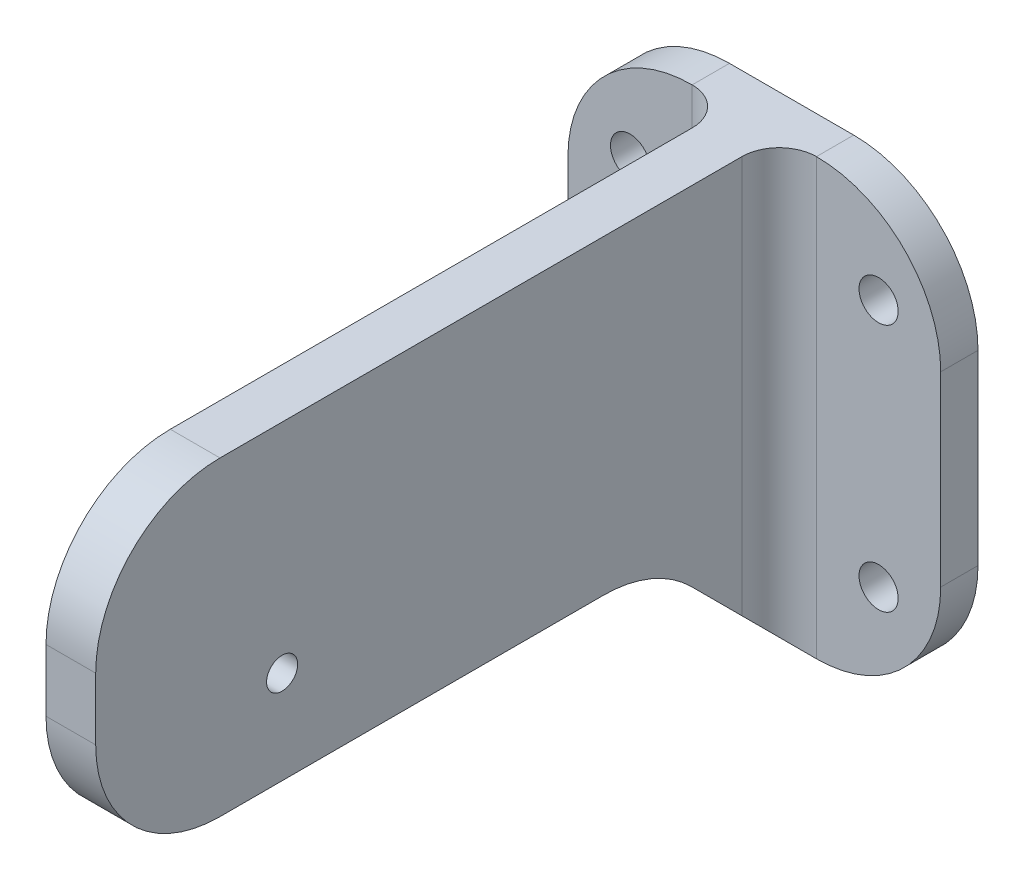
SolidWorks part; units mm, degrees
material "Du"
ref_plane "Front Plane" through (0, 0, 0) normal (0, 0, 1) x (1, 0, 0)
ref_plane "Top Plane" through (0, 0, 0) normal (0, 1, 0) x (1, 0, 0)
ref_plane "Right Plane" through (0, 0, 0) normal (1, 0, 0) x (0, 0, -1)
sketch "Sketch1" plane through (0, 0, 0) normal (0, 0, 1) x (1, 0, 0)
  line L1 (-15, 17.5) -> (15, 17.5)
  line L2 (-15, 17.5) -> (-15, -17.5)
  line L3 (-15, -17.5) -> (15, -17.5)
  line L4 (15, 17.5) -> (15, -17.5)
  line L5 (-15, 17.5) -> (15, -17.5) construction
  line L6 (-15, -17.5) -> (15, 17.5) construction
  point P0 (0, 0)
  dimension "D1" = 30
  dimension "D2" = 35
extrude "Boss-Extrude1" add sketch "Sketch1" along normal blind 3
sketch "Sketch2" plane through (0, 0, 3) normal (0, 0, 1) x (1, 0, 0)
  line L0 (-15, -17.5) -> (15, -17.5) construction
  line L1 (-2, 17.5) -> (2, 17.5)
  line L2 (-2, 17.5) -> (-2, -17.5)
  line L3 (-2, -17.5) -> (2, -17.5)
  line L4 (2, 17.5) -> (2, -17.5)
  line L5 (-2, 17.5) -> (2, -17.5) construction
  line L6 (-2, -17.5) -> (2, 17.5) construction
  point P0 (0, 0)
  dimension "D1" = 4
extrude "Boss-Extrude2" add sketch "Sketch2" along normal blind 55
fillet "Fillet1" radius 10 2 edges at (0, 17.5, 58) (0, -17.5, 58)
sketch "Sketch3" plane through (0, 0, 3) normal (0, 0, 1) x (1, 0, 0)
  circle A0 centre (-10, 10) radius 1.575
  circle A1 centre (10, -10) radius 1.575
  circle A2 centre (10, 10) radius 1.575
  circle A3 centre (-10, -10) radius 1.575
  dimension "D1" = 3.15
fillet "Fillet2" radius 10 4 edges at (-15, -17.5, 1.5) (15, -17.5, 1.5) (15, 17.5, 1.5) (-15, 17.5, 1.5)
extrude "Cut-Extrude1" cut sketch "Sketch3" against normal blind 55
sketch "Sketch4" plane through (2, 0, 0) normal (1, 0, 0) x (0, 0, -1)
  line L0 (-58, -7.5) -> (-58, 7.5) construction
  circle A0 centre (-43, 0) radius 1.25
  dimension "D1" = 2.5
  dimension "D2" = 15
extrude "Cut-Extrude2" cut sketch "Sketch4" against normal blind 55
sketch "Sketch5" plane through (2, 0, 0) normal (1, 0, 0) x (0, 0, -1)
  line L0 (-48, -17.5) -> (-3, -17.5) construction
  line L1 (-13, -17.5) -> (-66.6146, -17.5)
  line L2 (-13, -17.5) -> (-13, -7.5)
  line L3 (-13, -7.5) -> (-66.6146, -7.5)
  line L4 (-66.6146, -17.5) -> (-66.6146, -7.5)
  line L5 (-3, -17.5) -> (-3, 17.5) construction
  dimension "D1" = 10
  dimension "D2" = 10
extrude "Cut-Extrude3" cut sketch "Sketch5" against normal blind 55
fillet "Fillet3" radius 10 1 edges at (0, -7.5, 58)
sketch "Sketch6" plane through (2, 0, 0) normal (1, 0, 0) x (0, 0, -1)
  line L0 (-13, -7.5) -> (-3, -17.5)
  line L1 (-3, -17.5) -> (-13, -17.5)
  line L2 (-13, -17.5) -> (-13, -7.5)
extrude "Cut-Extrude4" cut sketch "Sketch6" against normal blind 55
fillet "Fillet4" radius 10 1 edges at (0, -7.5, 13)
fillet "Fillet5" radius 3 2 edges at (2, 0, 3) (-2, 0, 3)
